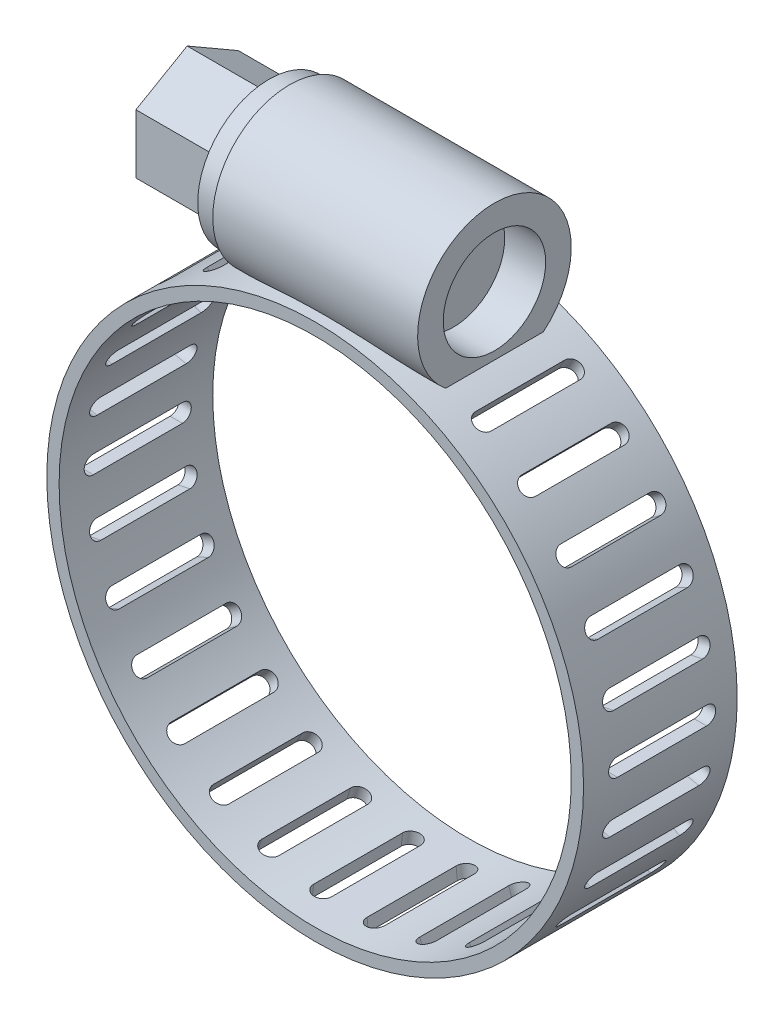
SolidWorks part; units mm, degrees
ref_plane "Front Plane" through (0, 0, 0) normal (0, 0, 1) x (1, 0, 0)
ref_plane "Top Plane" through (0, 0, 0) normal (0, 1, 0) x (1, 0, 0)
ref_plane "Right Plane" through (0, 0, 0) normal (1, 0, 0) x (0, 0, -1)
sketch "Sketch1" plane through (0, 0, 0) normal (0, 0, 1) x (1, 0, 0)
  circle A0 centre (0, 0) radius 15.875
  circle A1 centre (0, 0) radius 16.637
  dimension "D1" = 31.75
  dimension "D2" = 0.762
extrude "Boss-Extrude1" add sketch "Sketch1" along normal blind 9.525
sketch "Sketch2" plane through (0, 0, 0) normal (1, 0, 0) x (0, 0, -1)
  line L0 (-7.4106, 0) -> (-1.8906, 0) construction
  line L1 (-7.4106, 0.5595) -> (-1.8906, 0.5595)
  line L2 (-7.4106, -0.5595) -> (-1.8906, -0.5595)
  arc A0 (-7.4106, 0.5595) -> (-7.4106, -0.5595) centre (-7.4106, 0) ccw
  arc A1 (-1.8906, -0.5595) -> (-1.8906, 0.5595) centre (-1.8906, 0) ccw
  point P3 (-4.6506, 0)
extrude "Cut-Extrude1" cut sketch "Sketch2" against normal through all
ref_axis "Axis1" through (0, 0, 9.525) along (0, 0, -1)
pattern_circular "CirPattern1" count 30 over 360 about axis through (0, 0, 9.525) along (0, 0, -1) of "Cut-Extrude1"
sketch "Sketch3" plane through (0, 0, 0) normal (1, 0, 0) x (0, 0, -1)
  line L0 (-9.525, 0) -> (0, 0) construction
  circle A0 centre (-4.7625, 19.05) radius 4.7625
  dimension "D1" = 9.525
  dimension "D2" = 19.05
  dimension "D3" = 4.7625
extrude "Boss-Extrude2" add sketch "Sketch3" against normal mid plane 12.7
sketch "Sketch4" plane through (-6.35, 0, 0) normal (-1, 0, 0) x (0, 0, 1)
  line L1 (4.7625, 22.7162) -> (1.5875, 20.8831)
  line L2 (1.5875, 20.8831) -> (1.5875, 17.2169)
  line L3 (1.5875, 17.2169) -> (4.7625, 15.3838)
  line L4 (4.7625, 15.3838) -> (7.9375, 17.2169)
  line L5 (7.9375, 17.2169) -> (7.9375, 20.8831)
  line L6 (7.9375, 20.8831) -> (4.7625, 22.7162)
  circle A0 centre (4.7625, 19.05) radius 3.175 construction
  dimension "D1" = 6.35
extrude "Boss-Extrude3" add sketch "Sketch4" along normal blind 6.35
sketch "Sketch5" plane through (-6.35, 0, 0) normal (-1, 0, 0) x (0, 0, 1)
  circle A0 centre (4.7625, 19.05) radius 4.4249
extrude "Boss-Extrude4" add sketch "Sketch5" along normal blind 1.27
sketch "Sketch6" plane through (6.35, 0, 0) normal (1, 0, 0) x (0, 0, -1)
  circle A0 centre (-4.7625, 19.05) radius 3.175
  dimension "D1" = 6.35
extrude "Cut-Extrude2" cut sketch "Sketch6" against normal blind 2.54
